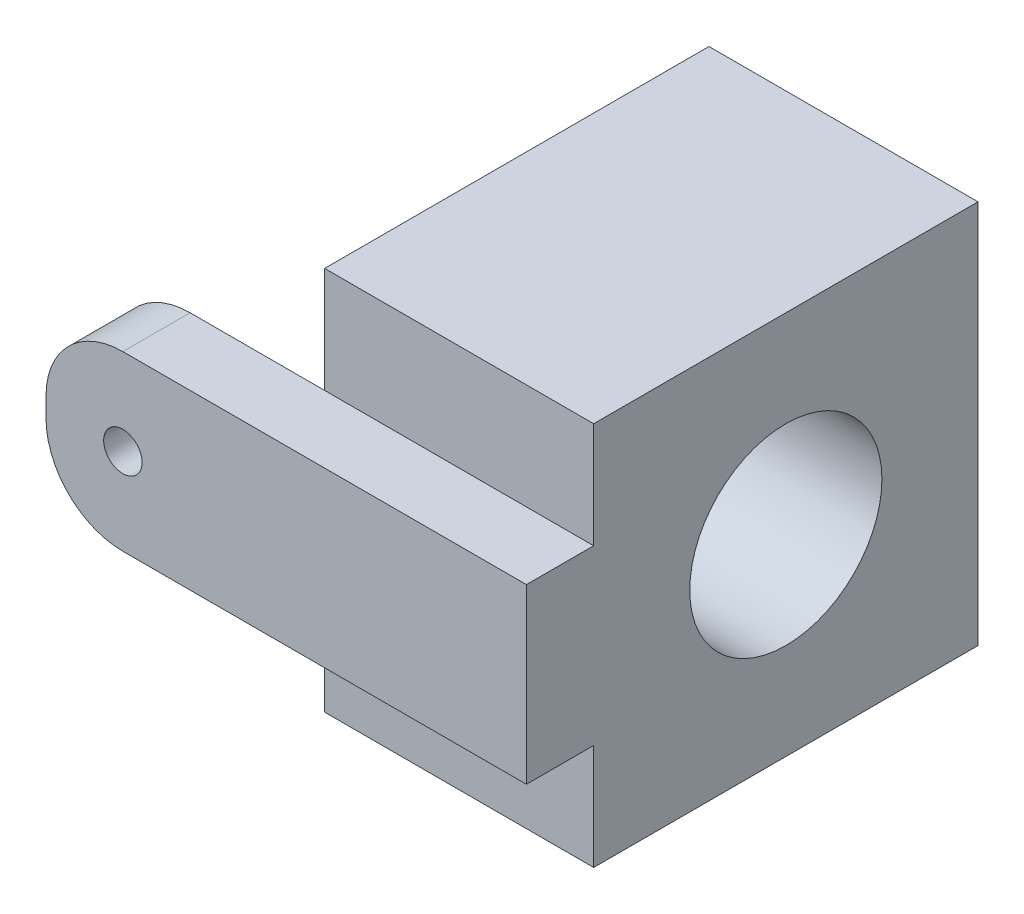
SolidWorks part; units mm, degrees
ref_plane "Ebene vorne" through (0, 0, 0) normal (0, 0, 1) x (1, 0, 0)
ref_plane "Ebene oben" through (0, 0, 0) normal (0, 1, 0) x (1, 0, 0)
ref_plane "Ebene rechts" through (0, 0, 0) normal (1, 0, 0) x (0, 0, -1)
sketch "Skizze1" plane through (0, 0, 0) normal (0, 1, 0) x (1, 0, 0)
  line L0 (0, -20) -> (0, 20) construction
  line L1 (14, 20) -> (-14, 20)
  line L2 (14, 20) -> (14, -20)
  line L3 (14, -20) -> (-14, -20)
  line L4 (-14, 20) -> (-14, -20)
  line L5 (14, 0) -> (-14, 0) construction
  point P8 (0, 0)
  dimension "D1" = 40
  dimension "D2" = 28
extrude "Aufsatz-Linear austragen1" add sketch "Skizze1" along normal blind 20 and the other way blind 20
sketch "Skizze2" plane through (14, 0, 0) normal (1, 0, 0) x (0, 0, -1)
  circle A0 centre (0, 0) radius 10
  dimension "D1" = 20
extrude "Schnitt-Linear austragen1" cut sketch "Skizze2" against normal through all
sketch "Skizze3" plane through (0, 0, 20) normal (0, 0, 1) x (1, 0, 0)
  line L0 (-11, 9) -> (-11, -9) construction
  line L1 (14, 9) -> (-36, 9)
  line L2 (14, 9) -> (14, -9)
  line L3 (14, -9) -> (-36, -9)
  line L4 (-36, 9) -> (-36, -9)
  line L5 (-36, 0) -> (14, 0) construction
  line L6 (14, -20) -> (14, 20) construction
  line L7 (25.85, 0) -> (-25.85, 0) construction
  dimension "D1" = 18
  dimension "D2" = 50
extrude "Aufsatz-Linear austragen2" add sketch "Skizze3" along normal blind 7
sketch "Skizze5" plane through (0, 0, 27) normal (0, 0, 1) x (1, 0, 0)
  line L0 (25.85, 0) -> (-25.85, 0) construction
  line L1 (-36, 9) -> (-36, -9) construction
  circle A0 centre (-28, 0) radius 2
  dimension "D1" = 4
  dimension "D2" = 8
extrude "Schnitt-Linear austragen2" cut sketch "Skizze5" against normal through all
fillet "Verrundung1" radius 8 2 edges at (-36, -9, 23.5) (-36, 9, 23.5)
